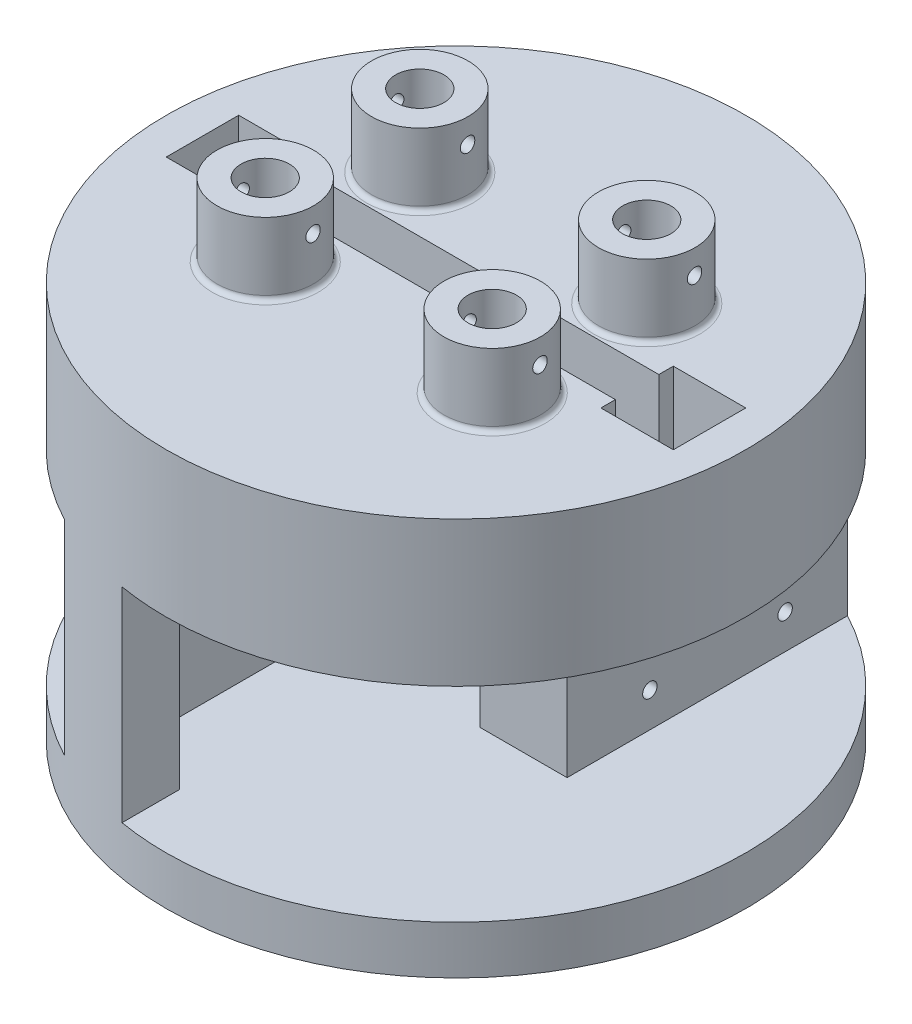
SolidWorks part; units mm, degrees
ref_plane "Front Plane" through (0, 0, 0) normal (0, 0, 1) x (1, 0, 0)
ref_plane "Top Plane" through (0, 0, 0) normal (0, 1, 0) x (1, 0, 0)
ref_plane "Right Plane" through (0, 0, 0) normal (1, 0, 0) x (0, 0, -1)
sketch "Sketch1" plane through (0, 0, 0) normal (0, 1, 0) x (1, 0, 0)
  circle A0 centre (0, 0) radius 60
  dimension "D1" = 120
extrude "Boss-Extrude1" add sketch "Sketch1" along normal blind 10
sketch "Sketch5" plane through (0, 10, 0) normal (0, 1, 0) x (1, 0, 0)
  line L0 (-73.7107, 0) -> (83.6973, 0) construction
  line L1 (0, -69.1137) -> (0, 62.4559) construction
  line L2 (0, 0) -> (20, 0) construction
  line L3 (0, 0) -> (-20, 0) construction
  line L4 (15, -47.3) -> (15, -5)
  line L5 (-15, 47.3) -> (23, 47.3)
  line L6 (-15, 47.3) -> (-15, 5)
  line L7 (-15, 5) -> (23, 5)
  line L8 (23, 47.3) -> (23, 5)
  line L9 (-15, 47.3) -> (23, 5) construction
  line L10 (-15, 5) -> (23, 47.3) construction
  line L11 (15, -47.3) -> (-23, -47.3)
  line L12 (-23, -47.3) -> (-23, -5)
  line L13 (15, -5) -> (-23, -5)
  line L15 (10, 0) -> (28, 0)
  line L16 (28, 53.066) -> (28, 0)
  line L20 (-28, -53.066) -> (-28, 0)
  line L22 (10, 59.1608) -> (10, 47.3)
  line L24 (10, 5) -> (10, 0)
  line L26 (-10, 0) -> (-10, -5)
  line L27 (-10, -47.3) -> (-10, -59.1608)
  line L28 (-10, 0) -> (-28, 0)
  line L29 (-20, 52.3) -> (28, 52.3) construction
  line L30 (-20, 52.3) -> (-20, 0) construction
  line L31 (28, 52.3) -> (28, 0) construction
  line L32 (20, -52.3) -> (20, 0) construction
  line L33 (20, -52.3) -> (-28, -52.3) construction
  line L34 (-28, -52.3) -> (-28, 0) construction
  line L35 (-20, 0) -> (28, 0) construction
  line L37 (20, 0) -> (-28, 0) construction
  line L38 (-10, 0) -> (5, 0)
  line L39 (-10, 0) -> (-10, -5)
  line L40 (-10, -5) -> (5, -5)
  line L41 (5, 0) -> (5, -5)
  line L42 (-5, 5) -> (10, 5)
  line L43 (-5, 5) -> (-5, 0)
  line L44 (-5, 0) -> (10, 0)
  line L45 (10, 5) -> (10, 0)
  circle A0 centre (0, 0) radius 60
  point P7 (4, 26.15)
  point P19 (0, 0)
  dimension "D10" = 120
  dimension "D1" = 20
  dimension "D2" = 20
  dimension "D4" = 42.3
  dimension "D5" = 5
  dimension "D6" = 5
  dimension "D7" = 38
  dimension "D11" = 20
  dimension "D12" = 10
  dimension "D9" = 10
  dimension "D13" = 5
  dimension "D8" = 5
  dimension "D3" = 2
extrude "Boss-Extrude5" add sketch "Sketch5" along normal blind 42.3 contours L7 L24 L15 L16 L22 L5 L8 | L27 L11 L12 L13 L26 L15 L20 A0 region at (-10.6184, 10, 53.2304) region at (10.6184, 10, -2.5)
sketch "Sketch6" plane through (28, 0, 0) normal (1, 0, 0) x (0, 0, -1)
  line L6 (26.15, 52.3) -> (26.15, 10) construction
  line L11 (5, 31.15) -> (47.3, 31.15) construction
  line L18 (12.15, 45.15) -> (40.15, 45.15) construction
  line L20 (5, 10) -> (47.3, 10)
  line L21 (5, 52.3) -> (5, 10)
  line L22 (47.3, 52.3) -> (5, 52.3)
  line L23 (47.3, 10) -> (47.3, 52.3)
  line L24 (5, 10) -> (47.3, 10)
  line L25 (5, 52.3) -> (5, 10)
  line L26 (47.3, 52.3) -> (5, 52.3)
  line L27 (47.3, 10) -> (47.3, 52.3)
  line L28 (12.15, 45.15) -> (12.15, 17.15) construction
  line L29 (12.15, 17.15) -> (40.15, 17.15) construction
  line L30 (40.15, 45.15) -> (40.15, 17.15) construction
  line L31 (12.15, 45.15) -> (40.15, 17.15) construction
  line L32 (12.15, 17.15) -> (40.15, 45.15) construction
  circle A4 centre (12.15, 45.15) radius 1.5
  circle A5 centre (40.15, 45.15) radius 1.5
  circle A6 centre (40.15, 17.15) radius 1.5
  circle A7 centre (12.15, 17.15) radius 1.5
  point P10 (26.15, 31.15)
  dimension "D1" = 0
  dimension "D2" = 3
  dimension "D3" = 28
  dimension "D4" = 28
extrude "Cut-Extrude1" cut sketch "Sketch6" against normal through all contours A4 | A7 | A6 | A5
pattern_circular "CirPattern1" count 2 over 360 about axis through (0, 10, 0) along (0, 1, 0) of "Cut-Extrude1"
sketch "Sketch8" plane through (0, 10, 0) normal (0, 1, 0) x (1, 0, 0)
  line L0 (10, 47.3) -> (23, 47.3) construction
  line L1 (23, 5) -> (-15, 5)
  line L2 (23, 5) -> (23, 47.3)
  line L3 (23, 47.3) -> (-15, 47.3)
  line L4 (-15, 5) -> (-15, 47.3)
  line L5 (-10, -47.3) -> (-23, -47.3) construction
  line L6 (-23, -5) -> (15, -5)
  line L7 (-23, -5) -> (-23, -47.3)
  line L8 (-23, -47.3) -> (15, -47.3)
  line L9 (15, -5) -> (15, -47.3)
  line L10 (-15, 26.15) -> (-39, 26.15) construction
  line L11 (15, -26.15) -> (39, -26.15) construction
  dimension "D1" = 38
  dimension "D2" = 38
  dimension "D3" = 24
  dimension "D4" = 24
sketch "Sketch3" plane through (0, 52.3, 0) normal (0, 1, 0) x (1, 0, 0)
  circle A11 centre (0, 0) radius 60
  dimension "D1" = 120
extrude "Boss-Extrude4" add sketch "Sketch3" along normal blind 30
sketch "Sketch4" plane through (0, 82.3, 0) normal (0, 1, 0) x (1, 0, 0)
  line L1 (-23.5, 16) -> (23.5, 16) construction
  line L2 (-23.5, 16) -> (-23.5, -16) construction
  line L3 (-23.5, -16) -> (23.5, -16) construction
  line L4 (23.5, 16) -> (23.5, -16) construction
  line L5 (-23.5, 16) -> (23.5, -16) construction
  line L6 (-23.5, -16) -> (23.5, 16) construction
  circle A0 centre (-23.5, 16) radius 5
  circle A1 centre (23.5, 16) radius 5
  circle A2 centre (23.5, -16) radius 5
  circle A3 centre (-23.5, -16) radius 5
  circle A4 centre (-23.5, 16) radius 10
  circle A5 centre (23.5, 16) radius 10
  circle A6 centre (23.5, -16) radius 10
  circle A7 centre (-23.5, -16) radius 10
  point P0 (0, 0)
  dimension "D3" = 10
  dimension "D1" = 47
  dimension "D2" = 32
  dimension "D4" = 5
extrude "Boss-Extrude6" add sketch "Sketch4" along normal blind 15
fillet "Fillet1" radius 1 4 edges at (23.5, 82.3, -6) (-23.5, 82.3, -6) (23.5, 82.3, 26) (-23.5, 82.3, 26)
sketch "Sketch7" plane through (0, 0, 0) normal (1, 0, 0) x (0, 0, -1)
  line L0 (0, 0) -> (0, 82.3) construction
  line L1 (60, 82.3) -> (-60, 82.3) construction
  line L2 (0, 82.3) -> (0, 92.3) construction
  line L3 (0, 92.3) -> (16, 92.3) construction
  line L4 (0, 92.3) -> (-16, 92.3) construction
  circle A0 centre (16, 92.3) radius 1.5
  circle A1 centre (-16, 92.3) radius 1.5
  dimension "Set screw OD" = 3
  dimension "D1" = 10
  dimension "D2" = 16
extrude "Cut-Extrude2" cut sketch "Sketch7" along normal through all both and the other way through all
sketch "Sketch9" plane through (0, 82.3, 0) normal (0, 1, 0) x (1, 0, 0)
  line L0 (-60, 0) -> (60, 0) construction
  line L1 (0, 60) -> (0, -60) construction
  line L3 (-45, 4.5) -> (45, 4.5)
  line L4 (-45, 4.5) -> (-45, -4.5)
  line L5 (-45, -4.5) -> (45, -4.5)
  line L6 (45, 4.5) -> (45, -4.5)
  line L7 (-45, 4.5) -> (45, -4.5) construction
  line L8 (-45, -4.5) -> (45, 4.5) construction
  line L9 (-52.5, 7.5) -> (-37.5, 7.5)
  line L10 (-52.5, 7.5) -> (-52.5, -7.5)
  line L11 (-52.5, -7.5) -> (-37.5, -7.5)
  line L12 (-37.5, 7.5) -> (-37.5, -7.5)
  line L13 (-52.5, 7.5) -> (-37.5, -7.5) construction
  line L14 (-52.5, -7.5) -> (-37.5, 7.5) construction
  line L15 (37.5, 7.5) -> (52.5, 7.5)
  line L16 (37.5, 7.5) -> (37.5, -7.5)
  line L17 (37.5, -7.5) -> (52.5, -7.5)
  line L18 (52.5, 7.5) -> (52.5, -7.5)
  line L19 (37.5, 7.5) -> (52.5, -7.5) construction
  line L20 (37.5, -7.5) -> (52.5, 7.5) construction
  circle A0 centre (0, 0) radius 60 construction
  point P8 (0, 0)
  point P13 (-45, 0)
  point P18 (45, 0)
  point P23 (-34.0136, -8.8529)
  point P24 (0, 0)
  point P25 (43.8872, 0)
  dimension "D1" = 90
  dimension "D2" = 9
  dimension "D3" = 15
  dimension "D4" = 45
extrude "Cut-Extrude6" cut sketch "Sketch9" against normal up to surface (30 mm away) contours L12 L9 L10 L11 L5 L4 L3 | L16 L3 L12 L5 | L12 L3 L4 L5 | L3 L16 L5 L6 | L18 L15 L16 L3 L6 L5 L17 region at (-46.6071, 82.3, 0) region at (-41.25, 82.3, 0) region at (0, 82.3, 0) region at (46.6071, 82.3, 0) region at (41.25, 82.3, 0) up to face at (0, 52.3, 0)
sketch "Sketch10" plane through (10, 0, 0) normal (-1, 0, 0) x (0, 0, 1)
  line L0 (-2.25, 52.3) -> (-2.25, 31.15) construction
  line L1 (-4.5, 52.3) -> (0, 52.3) construction
  circle A0 centre (-2.25, 31.15) radius 1
  dimension "Gt2 belt ID" = 2
  dimension "D1" = 21.15
sketch "Sketch11" plane through (0, 0, 0) normal (0, 0, -1) x (-1, 0, 0)
  line L1 (10, 52.3) -> (28, 52.3)
  line L2 (10, 52.3) -> (10, 10)
  line L3 (10, 10) -> (28, 10)
  line L4 (28, 52.3) -> (28, 10)
extrude "Boss-Extrude7" add sketch "Sketch11" along normal blind 5
sketch "Sketch12" plane through (-28, 0, 0) normal (-1, 0, 0) x (0, 0, 1)
  line L0 (-5, 52.3) -> (-5, 10) construction
  line L1 (-5, 52.3) -> (-5, 10)
sketch "Sketch14" plane through (0, 0, 0) normal (0, 0, 1) x (1, 0, 0)
  line L4 (10, 10) -> (28, 10)
  line L5 (28, 10) -> (28, 52.3)
  line L6 (28, 52.3) -> (10, 52.3)
  line L7 (10, 52.3) -> (10, 10)
  line L8 (10, 10) -> (28, 10)
  line L9 (28, 10) -> (28, 52.3)
  line L10 (28, 52.3) -> (10, 52.3)
  line L11 (10, 52.3) -> (10, 10)
  dimension "D1" = 0
extrude "Boss-Extrude8" add sketch "Sketch14" along normal blind 5
sketch "Sketch16" plane through (0, 82.3, 0) normal (0, 1, 0) x (1, 0, 0)
  line L0 (-37.5, -4.5) -> (-37.5, -7.5) construction
  line L1 (-52.5, 7.5) -> (-37.5, 7.5)
  line L2 (-52.5, 7.5) -> (-52.5, -7.5)
  line L3 (-52.5, -7.5) -> (-37.5, -7.5)
  line L4 (-37.5, 7.5) -> (-37.5, -7.5)
  line L5 (-52.5, -7.5) -> (-37.5, -7.5) construction
  line L7 (37.5, 7.5) -> (52.5, 7.5)
  line L8 (37.5, 7.5) -> (37.5, -7.5)
  line L9 (37.5, -7.5) -> (52.5, -7.5)
  line L10 (52.5, 7.5) -> (52.5, -7.5)
sketch "Sketch18" plane through (0, 52.3, 0) normal (0, 1, 0) x (1, 0, 0)
  line L4 (-10, -4.5) -> (-10, 4.5)
  line L5 (-10, 4.5) -> (-28, 4.5)
  line L6 (-28, 4.5) -> (-28, -4.5)
  line L7 (-28, -4.5) -> (-10, -4.5)
  line L8 (-10, -4.5) -> (-10, 4.5)
  line L9 (-10, 4.5) -> (-28, 4.5)
  line L10 (-28, 4.5) -> (-28, -4.5)
  line L11 (-28, -4.5) -> (-10, -4.5)
  line L12 (10, 4.5) -> (10, -4.5)
  line L13 (10, -4.5) -> (28, -4.5)
  line L14 (28, -4.5) -> (28, 4.5)
  line L15 (28, 4.5) -> (10, 4.5)
  line L16 (10, 4.5) -> (10, -4.5)
  line L17 (10, -4.5) -> (28, -4.5)
  line L18 (28, -4.5) -> (28, 4.5)
  line L19 (28, 4.5) -> (10, 4.5)
  dimension "D1" = 0
  dimension "D2" = 0
extrude "Boss-Extrude9" add sketch "Sketch18" along normal blind 15
sketch "Sketch19" plane through (-28, 0, 0) normal (-1, 0, 0) x (0, 0, 1)
  circle A0 centre (0, 67.5) radius 2.5
  point P2 (0, 0)
  dimension "D2" = 5
  dimension "D1" = 67.5
extrude "Cut-Extrude7" cut sketch "Sketch19" against normal blind 5 and the other way blind 30
mirror "Mirror1" about plane through (0, 0, 0) normal (1, 0, 0) of "Cut-Extrude7"
